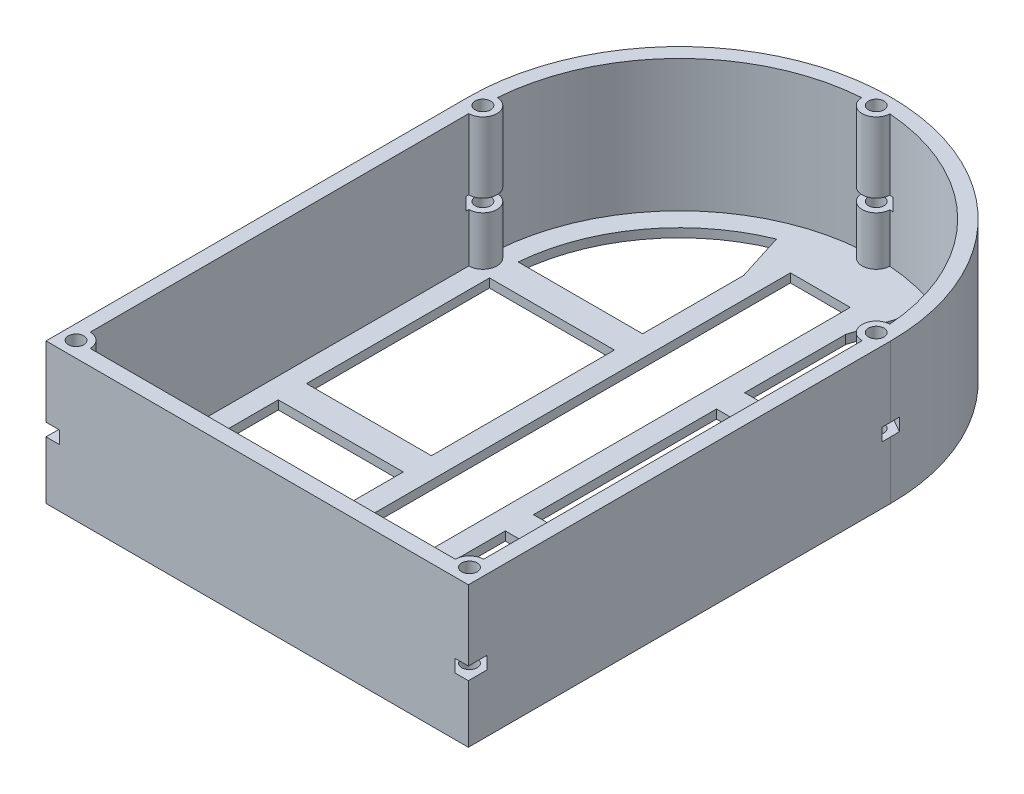
SolidWorks part; units mm, degrees
ref_plane "Front Plane" through (0, 0, 0) normal (0, 0, 1) x (1, 0, 0)
ref_plane "Top Plane" through (0, 0, 0) normal (0, 1, 0) x (1, 0, 0)
ref_plane "Right Plane" through (0, 0, 0) normal (1, 0, 0) x (0, 0, -1)
sketch "Sketch1" plane through (0, 0, 0) normal (0, 1, 0) x (1, 0, 0)
  line L1 (-30, 0) -> (30, 0) construction
  line L2 (-30, 0) -> (-30, -60)
  line L3 (-30, -60) -> (30, -60)
  line L4 (30, 0) -> (30, -60)
  line L5 (-30, 0) -> (30, -60) construction
  line L6 (-30, -60) -> (30, 0) construction
  line L9 (27.785, -57.785) -> (27.94, -57.785)
  line L10 (27.94, -55.785) -> (27.94, -2)
  line L11 (-25.94, -57.785) -> (25.94, -57.785)
  line L12 (-27.94, -2) -> (-27.94, -55.785)
  arc A0 (-30, 0) -> (30, 0) centre (0, 0) cw
  circle A1 centre (27.94, 0) radius 1.1
  circle A2 centre (-27.94, 0) radius 1.1
  circle A3 centre (0, 27.94) radius 1.1
  circle A4 centre (-27.94, -57.785) radius 1.1
  circle A5 centre (27.94, -57.785) radius 1.1
  arc A7 (27.8684, 1.9987) -> (27.94, -2) centre (27.94, 0) ccw
  arc A8 (27.94, -55.785) -> (25.94, -57.785) centre (27.94, -57.785) ccw
  arc A9 (-25.94, -57.785) -> (-27.94, -55.785) centre (-27.94, -57.785) ccw
  arc A11 (-1.9987, 27.8684) -> (1.9987, 27.8684) centre (0, 27.94) ccw
  circle A12 centre (0, 27.94) radius 2 construction
  circle A13 centre (27.94, 0) radius 2 construction
  arc A14 (1.9987, 27.8684) -> (27.8684, 1.9987) centre (0, 0) cw
  arc A15 (29.9391, -0.0609) -> (29.94, 0) centre (27.94, 0) ccw
  circle A16 centre (27.94, -57.785) radius 2 construction
  circle A17 centre (-27.94, -57.785) radius 2 construction
  arc A18 (-27.8684, 1.9987) -> (-1.9987, 27.8684) centre (0, 0) cw
  arc A19 (-27.94, -2) -> (-27.8684, 1.9987) centre (-27.94, 0) ccw
  point P0 (0, -30)
  dimension "D3" = 27.94
  dimension "D4" = 2.2
  dimension "D1" = 60
  dimension "D2" = 60
  dimension "D5" = 27.94
  dimension "D6" = 27.94
  dimension "D7" = 57.785
  dimension "D8" = 0.9
extrude "Boss-Extrude1" add sketch "Sketch1" against normal blind 20 contours A0 L2 L3 L4 A5 A4 A3 A2 A1 L12 A19 A18 A11 A14 A7 L10 A8 L11 A9 region at (0, 0, -29.8918)
sketch "Sketch2" plane through (0, -20, 0) normal (0, -1, 0) x (1, 0, 0)
  line L0 (-7.25, 53) -> (-7.25, 32)
  line L1 (-4.25, 50) -> (4.25, 50)
  line L2 (-4.25, 50) -> (-4.25, -20)
  line L3 (30, 0) -> (30, 60)
  line L4 (30, 60) -> (-30, 60)
  line L5 (-30, 60) -> (-30, 0)
  line L6 (30, 0) -> (30, 60)
  line L7 (30, 60) -> (-30, 60)
  line L8 (-30, 60) -> (-30, 0)
  line L9 (-4.25, -20) -> (4.25, -20)
  line L10 (4.25, 50) -> (4.25, -20)
  line L11 (-4.25, 50) -> (4.25, -20) construction
  line L12 (-4.25, -20) -> (4.25, 50) construction
  line L13 (-5.153, -23) -> (5.153, -23) construction
  line L14 (7.25, 53) -> (7.25, 32)
  line L16 (0, 0) -> (-7.5159, -23.8435) construction
  line L17 (25, 2) -> (25, 28)
  line L18 (0, 0) -> (7.5159, -23.8435) construction
  line L19 (25, 55) -> (7.25, 55)
  line L20 (-25, 55) -> (-25, 32)
  line L22 (-7.25, 53) -> (-7.25, 55)
  line L23 (5.153, -23) -> (5.5843, -24.3683) construction
  line L24 (-5.153, -23) -> (-5.5843, -24.3683) construction
  line L25 (-7.25, 53) -> (-7.25, -23) construction
  line L26 (-7.25, -23) -> (7.25, -23) construction
  line L27 (7.25, 53) -> (7.25, -23) construction
  line L28 (0, -6.6526) -> (-5.6084, -24.4448) construction
  line L29 (0, -6.6526) -> (5.6084, -24.4448) construction
  line L30 (-7.25, -16.3474) -> (-9.3993, -23.1658)
  line L31 (7.25, 53) -> (7.25, 55)
  line L32 (7.25, -16.3474) -> (9.3993, -23.1658)
  line L34 (-7.25, 55) -> (-25, 55)
  line L35 (25, 55) -> (-25, 55) construction
  line L36 (-7.25, 53) -> (7.25, 53) construction
  line L37 (-25, 0) -> (-7.25, 0) construction
  line L38 (25, 0) -> (7.25, 0) construction
  line L39 (7.25, 30) -> (25, 30) construction
  line L40 (-7.25, 30) -> (-25, 30) construction
  line L41 (-24.9199, -2) -> (-7.25, -2)
  line L42 (25, 2) -> (7.25, 2)
  line L43 (-7.25, 32) -> (-25, 32)
  line L44 (7.25, 28) -> (25, 28)
  line L45 (-25, 2) -> (-7.25, 2)
  line L46 (24.9199, -2) -> (7.25, -2)
  line L47 (-7.25, 28) -> (-25, 28)
  line L48 (7.25, 32) -> (25, 32)
  line L49 (7.25, 2) -> (7.25, 0) construction
  line L50 (7.25, -2) -> (7.25, -16.3474)
  line L51 (7.25, 0) -> (7.25, -2) construction
  line L52 (-7.25, 0) -> (-7.25, -2) construction
  line L53 (-7.25, -2) -> (-7.25, -16.3474)
  line L54 (-7.25, 2) -> (-7.25, 0) construction
  line L55 (-7.25, 32) -> (-7.25, 30) construction
  line L56 (-7.25, 28) -> (-7.25, 2)
  line L57 (-7.25, 30) -> (-7.25, 28) construction
  line L58 (7.25, 32) -> (7.25, 30) construction
  line L59 (7.25, 28) -> (7.25, 2)
  line L60 (7.25, 30) -> (7.25, 28) construction
  line L61 (-25, 32) -> (-25, 30) construction
  line L62 (-25, 28) -> (-25, 2)
  line L63 (-25, 55) -> (-25, 0) construction
  line L64 (-25, 30) -> (-25, 28) construction
  line L65 (25, 30) -> (25, 32) construction
  line L66 (25, 32) -> (25, 55)
  line L67 (25, 0) -> (25, 55) construction
  line L68 (25, 28) -> (25, 30) construction
  line L69 (25, 0) -> (25, 2) construction
  line L70 (-25, 2) -> (-25, 0) construction
  line L71 (9.3993, -23.1658) -> (9.4234, -23.2422) construction
  line L72 (-9.3993, -23.1658) -> (-9.4234, -23.2422) construction
  line L73 (-25, -2) -> (-24.9199, -2) construction
  line L74 (-25, -2) -> (-7.25, -2) construction
  line L75 (25, -2) -> (24.9199, -2) construction
  line L76 (25, -2) -> (7.25, -2) construction
  arc A0 (-24.9199, -2) -> (-9.3993, -23.1658) centre (0, 0) ccw
  arc A1 (-30, 0) -> (30, 0) centre (0, 0) ccw
  arc A2 (-30, 0) -> (30, 0) centre (0, 0) ccw
  arc A3 (-5.5843, -24.3683) -> (5.5843, -24.3683) centre (0, 0) ccw construction
  arc A4 (-25, 0) -> (25, 0) centre (0, 0) ccw construction
  arc A5 (9.3993, -23.1658) -> (24.9199, -2) centre (0, 0) ccw
  arc A6 (24.9199, -2) -> (25, 0) centre (0, 0) ccw construction
  arc A7 (-25, 0) -> (-24.9199, -2) centre (0, 0) ccw construction
  point P0 (0, 15)
  dimension "D2" = 8.5
  dimension "D3" = 70
  dimension "D4" = 15
  dimension "D7" = 30
  dimension "D1" = 0
  dimension "D5" = 3
  dimension "D6" = 5
  dimension "D8" = 2
  dimension "D9" = 2
  dimension "D10" = 2
extrude "Boss-Extrude2" add sketch "Sketch2" against normal blind 1.25
sketch "Sketch3" plane through (0, 0, 0) normal (0, 1, 0) x (1, 0, 0)
  line L0 (-30, -60) -> (30, -60) construction
  line L1 (2.4249, 27.94) -> (1.2124, 30.04)
  line L2 (1.2124, 30.04) -> (-1.2124, 30.04)
  line L3 (-1.2124, 30.04) -> (-2.4249, 27.94)
  line L4 (-1.8187, 26.89) -> (-1.2124, 25.84) construction
  line L5 (-1.2124, 25.84) -> (1.2124, 25.84)
  line L6 (1.8187, 26.89) -> (2.4249, 27.94) construction
  line L7 (27.94, -2.4249) -> (30.04, -1.2124)
  line L8 (30.04, -1.2124) -> (30.04, 1.2124)
  line L9 (30.04, 1.2124) -> (27.94, 2.4249)
  line L10 (26.89, 1.8187) -> (25.84, 1.2124) construction
  line L11 (25.84, 1.2124) -> (25.84, -1.2124)
  line L12 (25.84, -1.2124) -> (27.94, -2.4249)
  line L13 (30.2822, -58.4126) -> (29.6546, -56.0704)
  line L14 (29.6546, -56.0704) -> (27.3124, -55.4428)
  line L15 (27.3124, -55.4428) -> (25.5978, -57.1574)
  line L16 (25.5978, -57.1574) -> (26.2254, -59.4996)
  line L17 (26.2254, -59.4996) -> (28.5676, -60.1272)
  line L18 (29.4249, -59.2699) -> (30.2822, -58.4126) construction
  line L19 (-25.5978, -57.1574) -> (-27.3124, -55.4428)
  line L20 (-27.3124, -55.4428) -> (-29.6546, -56.0704)
  line L21 (-29.6546, -56.0704) -> (-30.2822, -58.4126)
  line L22 (-29.4249, -59.2699) -> (-28.5676, -60.1272) construction
  line L23 (-28.5676, -60.1272) -> (-26.2254, -59.4996)
  line L24 (-26.2254, -59.4996) -> (-25.5978, -57.1574)
  line L25 (-30.04, 1.2124) -> (-30.04, -1.2124)
  line L26 (-30.04, -1.2124) -> (-27.94, -2.4249)
  line L27 (-27.94, -2.4249) -> (-25.84, -1.2124)
  line L28 (-25.84, -1.2124) -> (-25.84, 1.2124)
  line L29 (-25.84, 1.2124) -> (-26.89, 1.8187) construction
  line L30 (-27.94, 2.4249) -> (-30.04, 1.2124)
  line L31 (-30.2822, -58.4126) -> (-30.9098, -60.7548)
  line L32 (-30.9098, -60.7548) -> (-28.5676, -60.1272)
  line L33 (-30.2822, -58.4126) -> (-29.4249, -59.2699) construction
  line L34 (28.5676, -60.1272) -> (30.9098, -60.7548)
  line L35 (30.9098, -60.7548) -> (30.2822, -58.4126)
  line L36 (28.5676, -60.1272) -> (29.4249, -59.2699) construction
  line L37 (-27.94, 2.4249) -> (-27.4431, 2.7117)
  line L38 (-27.4431, 2.7117) -> (-25.84, 1.2124)
  line L39 (-26.89, 1.8187) -> (-27.94, 2.4249) construction
  line L40 (27.94, 2.4249) -> (27.2976, 2.7958)
  line L41 (27.2976, 2.7958) -> (25.84, 1.2124)
  line L42 (27.94, 2.4249) -> (26.89, 1.8187) construction
  line L43 (-2.4249, 27.94) -> (-2.9234, 27.0765)
  line L44 (-2.9234, 27.0765) -> (-1.2124, 25.84)
  line L45 (1.2124, 25.84) -> (2.6648, 27.5244)
  line L46 (2.6648, 27.5244) -> (2.4249, 27.94)
  line L47 (-2.4249, 27.94) -> (-1.8187, 26.89) construction
  line L48 (1.2124, 25.84) -> (1.8187, 26.89) construction
  circle A0 centre (0, 27.94) radius 2.1 construction
  circle A1 centre (27.94, 0) radius 2.1 construction
  circle A2 centre (27.94, -57.785) radius 2.1 construction
  circle A3 centre (-27.94, -57.785) radius 2.1 construction
  circle A4 centre (-27.94, 0) radius 2.1 construction
  dimension "D1" = 4.2
  dimension "D2" = 45
  dimension "D3" = 45
extrude "Cut-Extrude1" cut sketch "Sketch3" against normal blind 1.8 from offset 10 offset against normal yes
